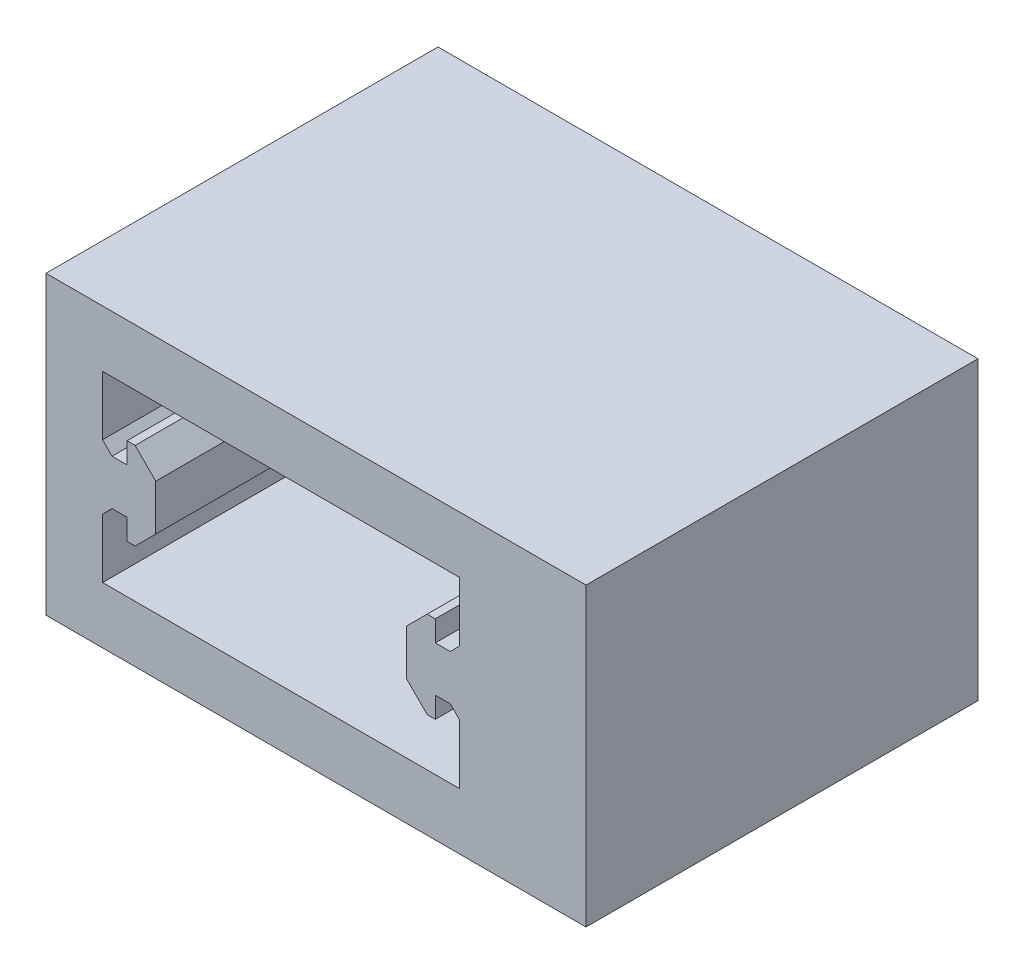
SolidWorks part; units mm, degrees
ref_plane "Front Plane" through (0, 0, 0) normal (0, 0, 1) x (1, 0, 0)
ref_plane "Top Plane" through (0, 0, 0) normal (0, 1, 0) x (1, 0, 0)
ref_plane "Right Plane" through (0, 0, 0) normal (1, 0, 0) x (0, 0, -1)
sketch "Sketch1" plane through (0, 0, 118.9397) normal (0, 0, 1) x (1, 0, 0)
  line L0 (-32.7804, 27.347) -> (-32.7804, 22.647) construction
  line L1 (-39.7804, 35.847) -> (22.2196, 35.847)
  line L2 (-39.7804, 35.847) -> (-39.7804, 1.847)
  line L3 (-39.7804, 1.847) -> (22.2196, 1.847)
  line L4 (22.2196, 35.847) -> (22.2196, 1.847)
  line L5 (-31.2804, 28.847) -> (-26.5804, 28.847) construction
  line L6 (-31.2804, 8.847) -> (-26.5804, 8.847) construction
  line L7 (7.2196, 15.047) -> (7.2196, 10.347) construction
  line L8 (-12.7804, 28.847) -> (-12.7804, 7.4462) construction
  line L9 (-14.2804, 28.847) -> (-11.2804, 28.847) construction
  line L10 (-39.7804, 18.847) -> (-11.2453, 18.847) construction
  line L11 (-33.2804, 29.347) -> (-33.2804, 22.5477)
  line L12 (-33.2804, 22.5477) -> (-32.1987, 21.447)
  line L13 (-32.1987, 21.447) -> (-30.4804, 21.447)
  line L14 (-30.4804, 21.447) -> (-30.4804, 23.847)
  line L15 (-30.4804, 23.847) -> (-29.5482, 23.847)
  line L16 (-29.5482, 23.847) -> (-27.1804, 21.4792)
  line L17 (-27.1804, 21.4792) -> (-27.1804, 16.2147)
  line L18 (-33.2804, 29.347) -> (7.7196, 29.347)
  line L20 (-26.739, 21.7449) -> (-29.341, 24.347) construction
  line L21 (-30.9804, 24.147) -> (-30.9804, 21.947) construction
  line L22 (-29.341, 24.347) -> (-30.7804, 24.347) construction
  line L23 (-26.6804, 21.6035) -> (-26.6804, 16.0905) construction
  line L24 (-30.9804, 21.947) -> (-32.0804, 21.947) construction
  line L26 (-29.5482, 13.847) -> (-27.1804, 16.2147)
  line L27 (-30.4804, 13.847) -> (-29.5482, 13.847)
  line L28 (-30.4804, 16.247) -> (-30.4804, 13.847)
  line L29 (-32.1987, 16.247) -> (-30.4804, 16.247)
  line L30 (-33.2804, 15.1463) -> (-32.1987, 16.247)
  line L31 (-33.2804, 8.347) -> (-33.2804, 15.1463)
  line L32 (-33.2804, 8.347) -> (7.7196, 8.347)
  line L33 (7.7196, 8.347) -> (7.7196, 15.1463)
  line L34 (7.7196, 15.1463) -> (6.6379, 16.247)
  line L35 (6.6379, 16.247) -> (4.9196, 16.247)
  line L36 (4.9196, 16.247) -> (4.9196, 13.847)
  line L37 (4.9196, 13.847) -> (3.9874, 13.847)
  line L38 (3.9874, 13.847) -> (1.6196, 16.2147)
  line L39 (1.6196, 21.4792) -> (1.6196, 16.2147)
  line L40 (3.9874, 23.847) -> (1.6196, 21.4792)
  line L41 (4.9196, 23.847) -> (3.9874, 23.847)
  line L42 (4.9196, 21.447) -> (4.9196, 23.847)
  line L43 (6.6379, 21.447) -> (4.9196, 21.447)
  line L44 (7.7196, 22.5477) -> (6.6379, 21.447)
  line L45 (7.7196, 29.347) -> (7.7196, 22.5477)
  point P55 (-12.7804, 18.847)
  dimension "D1" = 7
  dimension "D2" = 7
  dimension "D3" = 7
  dimension "D4" = 15
  dimension "D5" = 0.5
  dimension "D6" = 0.5
  dimension "D7" = 0.5
  dimension "D8" = 0.5
  dimension "D9" = 0.5
  dimension "D10" = 0.5
  dimension "D11" = 0.5
  dimension "D12" = 0.5
  dimension "D13" = 1.5433
extrude "Boss-Extrude1" add sketch "Sketch1" against normal blind 45 contours L2 L1 L4 L3 | L32 L33 L34 L35 L36 L37 L38 L39 L40 L41 L42 L43 L44 L45 L18 L11 L12 L13 L14 L15 L16 L17 L26 L27 L28 L29 L30 L31
